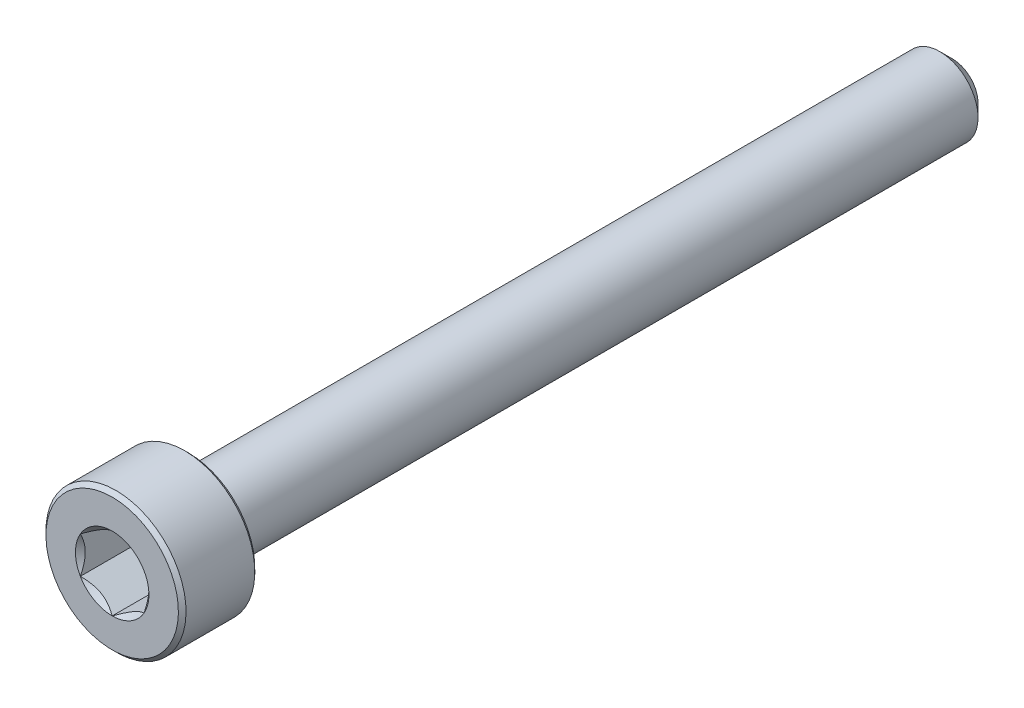
SolidWorks part; units mm, degrees
ref_plane "Front Plane" through (0, 0, 0) normal (0, 0, 1) x (1, 0, 0)
ref_plane "Top Plane" through (0, 0, 0) normal (0, 1, 0) x (1, 0, 0)
ref_plane "Right Plane" through (0, 0, 0) normal (1, 0, 0) x (0, 0, -1)
sketch "Sketch1" plane through (0, 0, 0) normal (1, 0, 0) x (0, 0, -1)
  line L0 (-16.5, 0) -> (16.5, 0) construction
  line L1 (16.5, 0) -> (16.5, 1) construction
  line L2 (16.5, 1) -> (16, 1.5) construction
  line L3 (16, 1.5) -> (16.125, 1.5) construction
  line L4 (16.125, 1.5) -> (-13.5, 1.5) construction
  line L5 (-13.5, 1.5) -> (-13.5, 2.75) construction
  line L6 (-13.5, 2.75) -> (-16.5, 2.75) construction
  line L7 (-16.5, 2.75) -> (-16.5, 0) construction
  line L8 (16.5, 1) -> (16.5, 1.5) construction
  line L9 (16.4688, 1.5541) -> (16.7188, 1.1211) construction
  line L10 (16.7188, 1.1211) -> (16.9688, 1.5541) construction
  line L11 (16.9688, 1.5541) -> (16.4688, 1.5541) construction
  line L12 (16.7188, 1.5541) -> (16.7187, 1.5) construction
  line L13 (16.7188, 1.1211) -> (16.7188, 1.1752) construction
  line L14 (16.6875, 1.1752) -> (16.75, 1.1752) construction
  line L15 (16.5, 1.5) -> (16.9375, 1.5) construction
  line L16 (16.4844, 1.5271) -> (16.9531, 1.5271) construction
  line L17 (16.5, 0) -> (16.5, -1.5) construction
  line L18 (-13.65, 2.75) -> (-13.5, 2.6) construction
  line L19 (-16.35, 2.75) -> (-16.5, 2.6) construction
  line L20 (-13.5, 1.5) -> (-13.5, 0) construction
  line L21 (-13.5, 0.75) -> (-3.5, 0.75) construction
  line L22 (-3.5, 0.75) -> (6.5, 0.75) construction
  line L23 (6.5, 0.75) -> (16.5, 0.75) construction
  line L24 (-3.5, 0.75) -> (-3.5, 1.5) construction
  line L25 (-3.5, 1.5) -> (-3.5, 2.75) construction
  line L26 (6.5, 0.75) -> (6.5, 2.75) construction
  point P0 (-16.5, 1.25)
  point P3 (15.25, 1.5)
  point P4 (0, 0)
  point P18 (6.5, 1.5)
  point P22 (16.7188, 1.1752)
  point P24 (16.125, 1.5)
  point P25 (16.7187, 1.5)
  point P28 (16.7187, 1.5271)
  point P29 (15.25, -1.5)
  point P30 (-3.5, 1.5)
  point P31 (-15, 2.75)
  point P37 (-14.025, 2.75)
  point P38 (-16.275, 2.75)
  point P45 (-3.5, 0.75)
  point P46 (6.5, 0.75)
  dimension "D1" = 45
  dimension "D2" = 0.0625
  dimension "D3" = 0.5
  dimension "D7" = 0.15
  dimension "D8" = 0.15
  dimension "D9" = 0.15
  dimension "D10" = 0.075
  dimension "D11" = 0.375
  dimension "Drive Size" = 2.5
  dimension "Head Diameter" = 5.5
  dimension "Head Height" = 3
  dimension "Thread Pitch" = 0.5
  dimension "Thread Major Diameter" = 3
  dimension "Length" = 30
  dimension "D12" = 0.375
  dimension "D4" = 1.25
sketch "Sketch2" plane through (0, 0, 0) normal (1, 0, 0) x (0, 0, -1)
  line L0 (-16.5, 0) -> (-16.5, 2.6)
  line L1 (-16.35, 2.75) -> (-13.65, 2.75)
  line L2 (-13.5, 2.6) -> (-13.5, 1.5)
  line L3 (-13.5, 1.5) -> (16, 1.5)
  line L4 (16, 1.5) -> (16.5, 1)
  line L5 (16.5, 1) -> (16.5, 0)
  line L6 (-13.65, 2.75) -> (-13.5, 2.6) construction
  line L7 (16.5, 0) -> (-16.5, 0)
  line L8 (-16.35, 2.75) -> (-16.5, 2.6) construction
  line L9 (-13.65, 2.75) -> (-13.5, 2.6)
  line L10 (-16.35, 2.75) -> (-16.5, 2.6)
revolve "Revolve1" add sketch "Sketch2" angle 360 about L7
sketch "Sketch3" plane through (0, 0, 16.5) normal (0, 0, 1) x (1, 0, 0)
  line L1 (1.25, -0.7217) -> (1.25, 0.7217)
  line L2 (1.25, 0.7217) -> (0, 1.4434)
  line L3 (0, 1.4434) -> (-1.25, 0.7217)
  line L4 (-1.25, 0.7217) -> (-1.25, -0.7217)
  line L5 (-1.25, -0.7217) -> (0, -1.4434)
  line L6 (0, -1.4434) -> (1.25, -0.7217)
  circle A0 centre (0, 0) radius 1.25 construction
extrude "Cut-Extrude1" cut sketch "Sketch3" against normal offset from surface (2 mm away) 1 up to face at (0, 2.6, 13.5)
sketch "Sketch4" plane through (0, 0, 16.5) normal (0, 0, 1) x (1, 0, 0)
  circle A0 centre (0, 0) radius 1.4434
extrude "Cut-Extrude2" cut sketch "Sketch4" against normal up to vertex (1.5 mm away) draft 45 up to point (0, 2.75, 15)
ref_plane "Plane1" [suppressed] through (0, 0, -16.125) normal (0, 0, 1) x (1, 0, 0)
split "Split1" [suppressed] bodies to split 106
sketch "Sketch6" [suppressed] plane through (0, 0, -16.5) normal (0, 0, -1) x (-1, 0, 0)
  circle A0 centre (0, 0) radius 1.5
curve "Helix/Spiral1" [suppressed] pitch 0.5 height 30.575 turns 61.15
sketch "Sketch7" [suppressed] plane through (0, 0, 0) normal (1, 0, 0) x (0, 0, -1)
  line L0 (16.4844, 1.5271) -> (16.9531, 1.5271)
  line L1 (16.9531, 1.5271) -> (16.75, 1.1752)
  line L2 (16.75, 1.1752) -> (16.6875, 1.1752)
  line L3 (16.6875, 1.1752) -> (16.4844, 1.5271)
sweep "Cut-Sweep1" [suppressed] cut profiles "Sketch7" path "Helix/Spiral1"
sketch "Sketch8" [suppressed] plane through (0, 0, 13.5) normal (0, 0, -1) x (-1, 0, 0)
  circle A0 centre (0, 0) radius 1.5
extrude "Boss-Extrude1" [suppressed] add sketch "Sketch8" along normal through all draft 45
equation "\"D2@Sketch1\" = \"Thread Pitch@Sketch1\" / 8"
equation "\"D3@Sketch1\"= \"Thread Pitch@Sketch1\""
equation "\"D4@Helix/Spiral1\" = \"Thread Pitch@Sketch1\""
equation "\"D7@Sketch1\" = \"Head Height@Sketch1\" * .05"
equation "\"D8@Sketch1\"=\"D7@Sketch1\""
equation "\"D9@Sketch1\"=\"D7@Sketch1\""
equation "\"D10@Sketch1\"=\"D7@Sketch1\"/2"
equation "\"D11@Sketch1\"=\"D10@Sketch1\"*5"
equation "\"D4@Sketch1\"=\"Thread Pitch@Sketch1\"*2.5"
equation "\"D12@Sketch1\"=\"Thread Pitch@Sketch1\"*.75"
